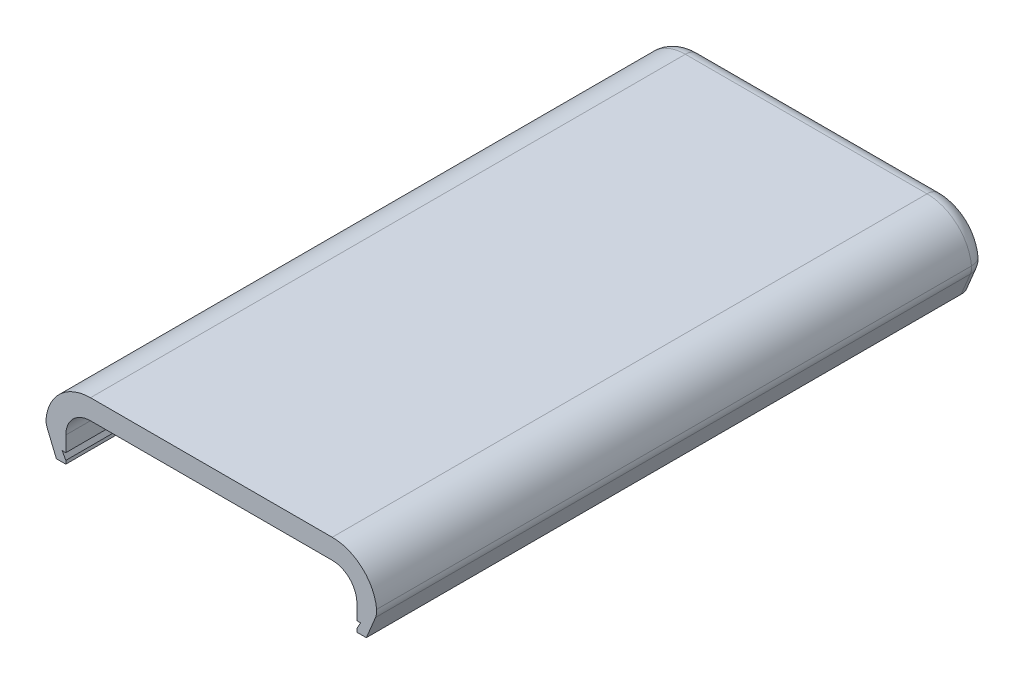
SolidWorks part; units mm, degrees
ref_plane "Front Plane" through (0, 0, 0) normal (0, 0, 1) x (1, 0, 0)
ref_plane "Top Plane" through (0, 0, 0) normal (0, 1, 0) x (1, 0, 0)
ref_plane "Right Plane" through (0, 0, 0) normal (1, 0, 0) x (0, 0, -1)
sketch "Sketch1" plane through (0, 0, 0) normal (0, 0, 1) x (1, 0, 0)
  line L0 (0, 0) -> (59.04, 0)
  line L1 (0, 0) -> (0, 4.82)
  line L2 (59.04, 0) -> (59.04, 4.82)
  line L3 (6.5, 11.32) -> (52.54, 11.32)
  arc A0 (0, 4.82) -> (6.5, 11.32) centre (6.5, 4.82) cw
  arc A1 (59.04, 4.82) -> (52.54, 11.32) centre (52.54, 4.82) ccw
  point P7 (0, 11.32)
  point P10 (59.04, 11.32)
  dimension "D3" = 6.5
  dimension "D1" = 11.32
  dimension "D2" = 59.04
extrude "Boss-Extrude1" add sketch "Sketch1" along normal blind 116.3
sketch "Sketch2" plane through (0, 0, 116.3) normal (0, 0, 1) x (1, 0, 0)
  line L11 (1.8, 1.9) -> (1.1, 1.9)
  line L12 (57.24, 0) -> (57.24, 4.82)
  line L13 (1.8, 4.82) -> (1.8, 0)
  line L14 (52.54, 9.52) -> (6.5, 9.52)
  line L15 (57.24, 0) -> (57.24, 4.82)
  line L16 (1.8, 4.82) -> (1.8, 0)
  line L17 (52.54, 9.52) -> (6.5, 9.52)
  line L18 (1.1, 1.9) -> (1.8, 0.63)
  line L19 (57.24, 1.9) -> (57.94, 1.9)
  line L20 (57.94, 1.9) -> (57.24, 0.63)
  line L21 (0, 4.82) -> (0, 0) construction
  line L22 (59.04, 0) -> (59.04, 4.82) construction
  line L23 (0, 0) -> (59.04, 0) construction
  line L24 (1.8, 0) -> (57.24, 0)
  arc A8 (57.24, 4.82) -> (52.54, 9.52) centre (52.54, 4.82) ccw
  arc A9 (6.5, 9.52) -> (1.8, 4.82) centre (6.5, 4.82) ccw
  arc A10 (57.24, 4.82) -> (52.54, 9.52) centre (52.54, 4.82) ccw
  arc A11 (6.5, 9.52) -> (1.8, 4.82) centre (6.5, 4.82) ccw
  line M9 (0, 0) -> (59.04, 0)
  dimension "D2" = 1.1
  dimension "D3" = 1.1
  dimension "D4" = 1.27
  dimension "D5" = 1.9
  dimension "D1" = 1.8
extrude "Cut-Extrude1" cut sketch "Sketch2" against normal offset from surface (112.7 mm away) 3.6 contours L17 A11 L16 L15 A10 M9 | L20 L19 L15 | L11 L18 L16 region at (1.5667, 1.4767, 116.3) region at (29.52, 4.6921, 116.3) region at (57.4733, 1.4767, 116.3) up to face at (29.52, 5.8287, 0)
sketch "Sketch3" plane through (0, 0, 116.3) normal (0, 0, 1) x (1, 0, 0)
  line L0 (52.54, 11.32) -> (57.0201, 8.6014)
  line L1 (57.0201, 8.6014) -> (59.04, 4.82)
  line L2 (6.5, 11.32) -> (2.648, 9.087)
  line L3 (-2, 4.82) -> (0, 0)
  line L4 (52.54, 13.32) -> (6.5, 13.32)
  line L5 (52.54, 13.32) -> (6.5, 13.32)
  line L6 (61.04, 4.82) -> (59.04, 0)
  line L7 (2.648, 9.087) -> (0, 4.82)
  line L8 (0, 0) -> (0, 4.82)
  line L9 (59.04, 0) -> (59.04, 4.82)
  line L11 (6.5, 11.32) -> (52.54, 11.32)
  arc A5 (61.04, 4.82) -> (52.54, 13.32) centre (52.54, 4.82) ccw
  arc A6 (6.5, 13.32) -> (-2, 4.82) centre (6.5, 4.82) ccw
  arc A7 (61.04, 4.82) -> (52.54, 13.32) centre (52.54, 4.82) ccw
  arc A8 (6.5, 13.32) -> (-2, 4.82) centre (6.5, 4.82) ccw
  dimension "D1" = 2
extrude "Boss-Extrude2" add sketch "Sketch3" against normal up to surface (116.3 mm away) up to face at (29.52, 5.8287, 0)
fillet "Fillet1" radius 3 7 edges at (-1, 2.41, 0) (-2, 4.82, 58.15) (61.04, 4.82, 58.15) (60.04, 2.41, 0) (0.4896, 10.8304, 0) (58.5504, 10.8304, 0) (29.52, 13.32, 0)
